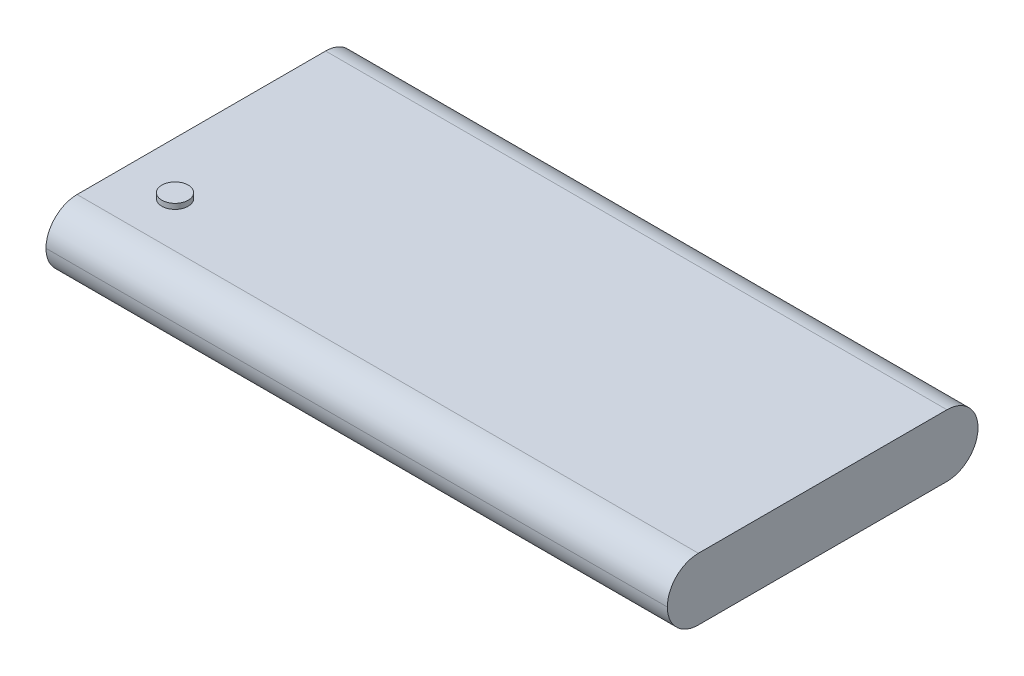
SolidWorks part; units mm, degrees
material "6061-T6 (SS)"
ref_plane "Front Plane" through (0, 0, 0) normal (0, 0, 1) x (1, 0, 0)
ref_plane "Top Plane" through (0, 0, 0) normal (0, 1, 0) x (1, 0, 0)
ref_plane "Right Plane" through (0, 0, 0) normal (1, 0, 0) x (0, 0, -1)
ref_axis "X AXIS" through (-88.99, 0, 0) along (1, 0, 0)
ref_axis "Y AXIS" through (0, -55, 0) along (0, 1, 0)
ref_axis "Z AXIS" through (0, 0, 55) along (0, 0, -1)
other "Freeze***"
sketch "Sketch1" plane through (0, 0, 0) normal (0, 1, 0) x (1, 0, 0)
  line L1 (-75, -37.5) -> (75, -37.5)
  line L2 (-75, -37.5) -> (-75, 37.5)
  line L3 (-75, 37.5) -> (75, 37.5)
  line L4 (75, -37.5) -> (75, 37.5)
  line L5 (0, 37.5) -> (0, -37.5) construction
  line L6 (-75, 0) -> (75, 0) construction
  point P0 (0, 0)
  dimension "D1" = 150
  dimension "D2" = 75
extrude "Boss-Extrude1" add sketch "Sketch1" along normal mid plane 15
fillet "Fillet1" radius 7.5 4 edges at (0, -7.5, -37.5) (0, 7.5, -37.5) (0, -7.5, 37.5) (0, 7.5, 37.5)
sketch "Sketch2" plane through (0, 7.5, 0) normal (0, 1, 0) x (1, 0, 0)
  line L0 (-75, 30) -> (-75, -30) construction
  circle A0 centre (-62.3, -19.05) radius 3.175
  dimension "D1" = 6.35
  dimension "D2" = 19.05
  dimension "D3" = 12.7
extrude "Boss-Extrude2" add sketch "Sketch2" along normal blind 1.27
